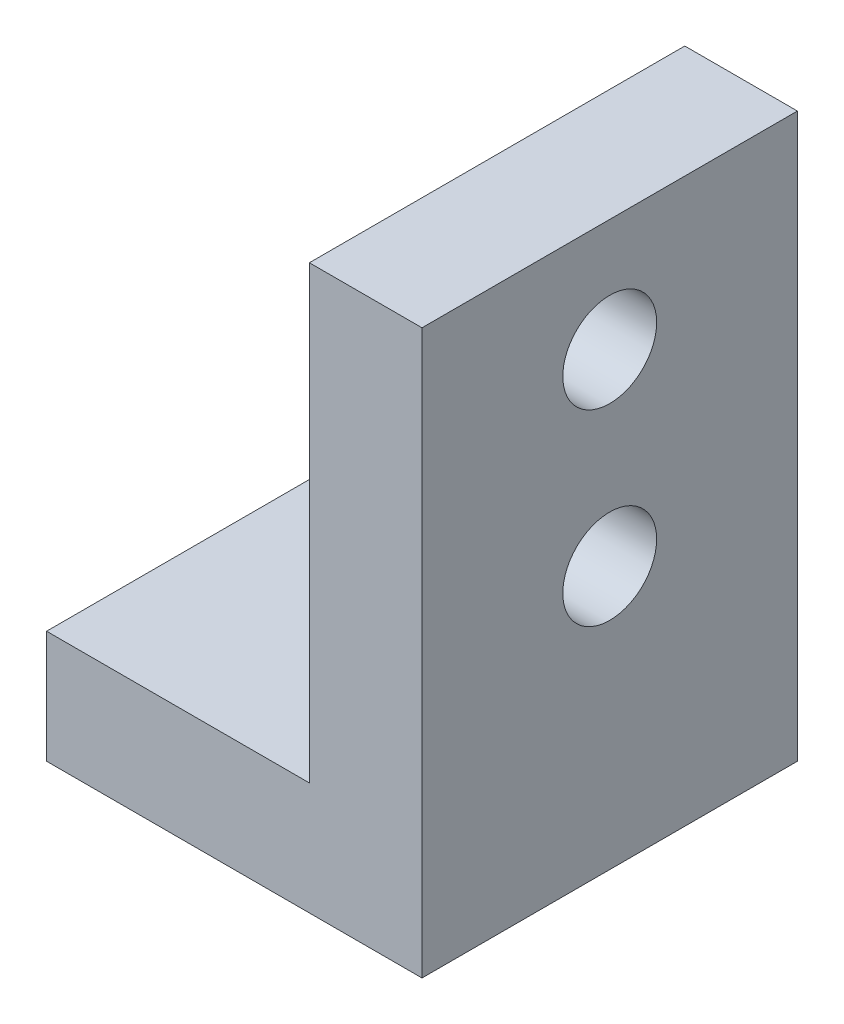
SolidWorks part; units mm, degrees
ref_plane "Plano frontal" through (0, 0, 0) normal (0, 0, 1) x (1, 0, 0)
ref_plane "Plano superior" through (0, 0, 0) normal (0, 1, 0) x (1, 0, 0)
ref_plane "Plano direito" through (0, 0, 0) normal (1, 0, 0) x (0, 0, -1)
sketch "Esboço1" plane through (0, 0, 0) normal (0, 0, 1) x (1, 0, 0)
  line L0 (0, 0) -> (0, -6)
  line L1 (0, -6) -> (20, -6)
  line L2 (20, -6) -> (20, 24)
  line L3 (20, 24) -> (14, 24)
  line L4 (14, 24) -> (14, 0)
  line L5 (14, 0) -> (0, 0)
  dimension "D1" = 20
  dimension "D2" = 30
  dimension "D3" = 6
  dimension "D4" = 6
extrude "Ressalto-extrusão1" add sketch "Esboço1" against normal blind 20
sketch "Esboço2" plane through (20, 0, 0) normal (1, 0, 0) x (0, 0, -1)
  line L0 (10, 24) -> (10, -6) construction
  line L1 (20, 24) -> (0, 24) construction
  line L2 (20, -6) -> (0, -6) construction
  circle A0 centre (10, 18) radius 2.5
  circle A1 centre (10, 8) radius 2.5
  point P10 (0, 0)
  point P11 (0, 0)
  point P12 (0, 0)
  dimension "D1" = 5
  dimension "D2" = 10
  dimension "D3" = 6
extrude "Corte-extrusão1" cut sketch "Esboço2" against normal through all
